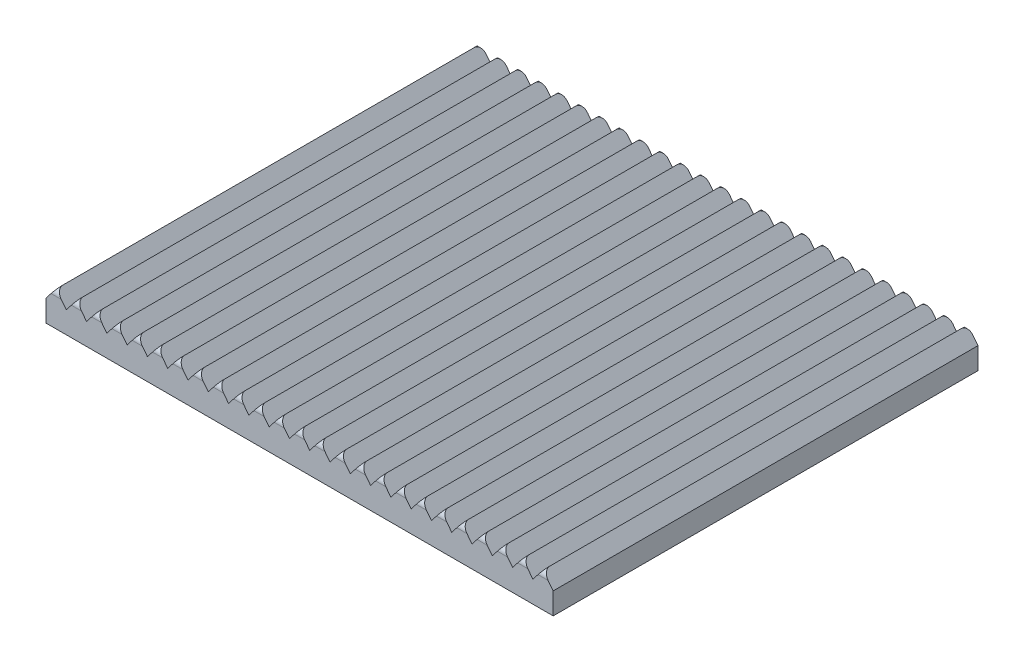
SolidWorks part; units mm, degrees
ref_plane "Front Plane" through (0, 0, 0) normal (0, 0, 1) x (1, 0, 0)
ref_plane "Top Plane" through (0, 0, 0) normal (0, 1, 0) x (1, 0, 0)
ref_plane "Right Plane" through (0, 0, 0) normal (1, 0, 0) x (0, 0, -1)
sketch "Sketch1" plane through (0, 0, 0) normal (0, 1, 0) x (1, 0, 0)
  line L6 (-29.25, 24.5) -> (29.25, 24.5)
  line L28 (-29.25, 24.5) -> (-29.25, -24.5)
  line L29 (-29.25, -24.5) -> (29.25, -24.5)
  line L30 (29.25, 24.5) -> (29.25, -24.5)
  line L31 (-29.25, 24.5) -> (29.25, -24.5) construction
  line L32 (-29.25, -24.5) -> (29.25, 24.5) construction
  circle A1 centre (0, 0) radius 3.1
  point P0 (0, 0)
  dimension "D3" = 6.2
  dimension "D1" = 58.5
  dimension "D2" = 49
extrude "Boss-Extrude1" add sketch "Sketch1" along normal blind 1.5
sketch "Sketch2" plane through (0, 0, -24.5) normal (0, 0, -1) x (-1, 0, 0)
  line L0 (-29.25, 1.5) -> (-29.25, 0) construction
  line L1 (-29.25, 1.5) -> (29.25, 1.5)
  line L2 (-29.25, 1.5) -> (-29.25, 2.5)
  line L4 (29.25, 1.5) -> (29.25, 2.5)
  line L5 (-1.17, 2.5) -> (0, 4)
  line L6 (0, 55) -> (0, -55) construction
  line L7 (1.17, 2.5) -> (0, 4)
  line L8 (1.17, 2.5) -> (2.34, 4)
  line L9 (3.51, 2.5) -> (2.34, 4)
  line L10 (3.51, 2.5) -> (4.68, 4)
  line L11 (5.85, 2.5) -> (4.68, 4)
  line L12 (5.85, 2.5) -> (7.02, 4)
  line L13 (8.19, 2.5) -> (7.02, 4)
  line L14 (8.19, 2.5) -> (9.36, 4)
  line L15 (10.53, 2.5) -> (9.36, 4)
  line L16 (10.53, 2.5) -> (11.7, 4)
  line L17 (12.87, 2.5) -> (11.7, 4)
  line L18 (12.87, 2.5) -> (14.04, 4)
  line L19 (15.21, 2.5) -> (14.04, 4)
  line L20 (15.21, 2.5) -> (16.38, 4)
  line L21 (17.55, 2.5) -> (16.38, 4)
  line L22 (17.55, 2.5) -> (18.72, 4)
  line L23 (19.89, 2.5) -> (18.72, 4)
  line L24 (19.89, 2.5) -> (21.06, 4)
  line L25 (22.23, 2.5) -> (21.06, 4)
  line L26 (22.23, 2.5) -> (23.4, 4)
  line L27 (24.57, 2.5) -> (23.4, 4)
  line L28 (24.57, 2.5) -> (25.74, 4)
  line L29 (26.91, 2.5) -> (25.74, 4)
  line L30 (26.91, 2.5) -> (28.08, 4)
  line L31 (29.25, 2.5) -> (28.08, 4)
  line L32 (-29.25, 2.5) -> (-28.08, 4)
  line L33 (-26.91, 2.5) -> (-28.08, 4)
  line L34 (-26.91, 2.5) -> (-25.74, 4)
  line L35 (-24.57, 2.5) -> (-25.74, 4)
  line L36 (-24.57, 2.5) -> (-23.4, 4)
  line L37 (-22.23, 2.5) -> (-23.4, 4)
  line L38 (-22.23, 2.5) -> (-21.06, 4)
  line L39 (-19.89, 2.5) -> (-21.06, 4)
  line L40 (-19.89, 2.5) -> (-18.72, 4)
  line L41 (-17.55, 2.5) -> (-18.72, 4)
  line L42 (-17.55, 2.5) -> (-16.38, 4)
  line L43 (-15.21, 2.5) -> (-16.38, 4)
  line L44 (-15.21, 2.5) -> (-14.04, 4)
  line L45 (-12.87, 2.5) -> (-14.04, 4)
  line L46 (-12.87, 2.5) -> (-11.7, 4)
  line L47 (-10.53, 2.5) -> (-11.7, 4)
  line L48 (-10.53, 2.5) -> (-9.36, 4)
  line L49 (-8.19, 2.5) -> (-9.36, 4)
  line L50 (-8.19, 2.5) -> (-7.02, 4)
  line L51 (-5.85, 2.5) -> (-7.02, 4)
  line L52 (-5.85, 2.5) -> (-4.68, 4)
  line L53 (-3.51, 2.5) -> (-4.68, 4)
  line L54 (-3.51, 2.5) -> (-2.34, 4)
  line L55 (-1.17, 2.5) -> (-2.34, 4)
  dimension "D1" = 1
  dimension "D2" = 1.5
  dimension "D3" = 13
extrude "Boss-Extrude2" add sketch "Sketch2" against normal blind 49
sketch "Sketch3" plane through (0, 0, 0) normal (0, -1, 0) x (-1, 0, 0)
  line L0 (0, 0.825) -> (0, -0.825) construction
  line L2 (-1.75, -2.5588) -> (-1.75, -5)
  line L3 (-1.75, -5) -> (1.75, -5)
  line L4 (1.75, -2.5588) -> (1.75, -5)
  arc A0 (1.75, -2.5588) -> (-1.75, -2.5588) centre (0, 0) ccw
  dimension "D2" = 6.2
  dimension "D1" = 3.5
  dimension "D3" = 5
  dimension "D4" = 1.75
extrude "Cut-Extrude1" cut sketch "Sketch3" against normal blind 1
chamfer "Chamfer2" distance 0.2 angle 45 1 edges at (0, 0, -3.1)
sketch "Sketch4" plane through (29.25, 0, 0) normal (1, 0, 0) x (0, 0, -1)
  line L1 (-24.5, 4) -> (-24.5, 2.5) construction
  line L2 (-24.5, 4) -> (24.5, 4) construction
  line L3 (-23.75, 4) -> (-24.5, 4)
  line L4 (-24.5, 4) -> (-24.5, 3.25)
  arc A0 (-24.5, 3.25) -> (-23.75, 4) centre (-23.75, 3.25) cw
extrude "Cut-Extrude3" cut sketch "Sketch4" against normal through all
mirror "Mirror1" about plane through (0, 0, 0) normal (0, 0, 1) of "Cut-Extrude3"
sketch "Sketch5" plane through (0, 1.5, 0) normal (0, -1, 0) x (1, 0, 0)
  circle A0 centre (0, 0) radius 3.1
extrude "Boss-Extrude3" add sketch "Sketch5" along normal blind 0.5
sketch "Sketch6" plane through (0, 1, 0) normal (0, -1, 0) x (1, 0, 0)
  line L1 (1.75, 5) -> (-1.75, 5)
  line L2 (1.75, 5) -> (1.75, 2.5588)
  line L3 (1.75, 2.5588) -> (-1.75, 2.5588)
  line L4 (-1.75, 5) -> (-1.75, 2.5588)
extrude "Cut-Extrude4" cut sketch "Sketch6" against normal blind 0.5
chamfer "Chamfer3" distance 1.5 angle 45 1 edges at (0, 0, 5)
